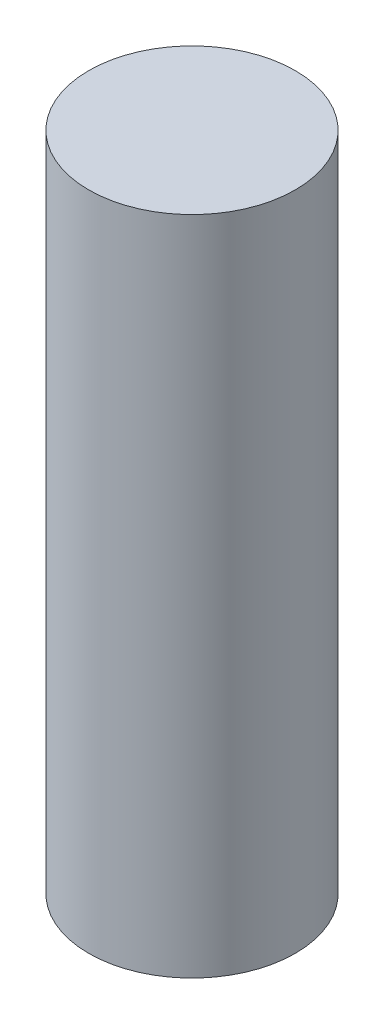
SolidWorks part; units mm, degrees
material "Silicon"
ref_plane "Front Plane" through (0, 0, 0) normal (0, 0, 1) x (1, 0, 0)
ref_plane "Top Plane" through (0, 0, 0) normal (0, 1, 0) x (1, 0, 0)
ref_plane "Right Plane" through (0, 0, 0) normal (1, 0, 0) x (0, 0, -1)
sketch "Main Parachute Bag Profile" plane through (0, 0, 0) normal (0, 1, 0) x (1, 0, 0)
  circle A0 centre (0, 0) radius 63.5
  dimension "D1" = 127
extrude "Main Parachute Bag Body" add sketch "Main Parachute Bag Profile" along normal blind 406.4 contours A0
equation "\"Packed Length\"=16"
equation "\"Packed Diameter\"= 5"
equation "\"D1@Main Parachute Bag Body\"=\"Packed Length\""
